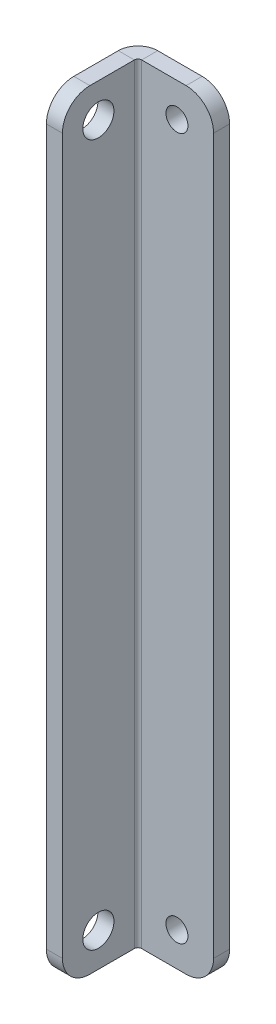
SolidWorks part; units mm, degrees
note: The reader was unsure of these and kept them because the rebuilt part matched: thickness of "Base-Flange1", "Edge-Flange1", "Sheet-Metal1", "Sheet-Metal2", "Sheet-Metal3", "Sheet-Metal4"; flange length of "Edge-Flange1".
ref_plane "Front Plane" through (0, 0, 0) normal (0, 0, 1) x (1, 0, 0)
ref_plane "Top Plane" through (0, 0, 0) normal (0, 1, 0) x (1, 0, 0)
ref_plane "Right Plane" through (0, 0, 0) normal (1, 0, 0) x (0, 0, -1)
sketch "Sketch1" plane through (0, 0, 0) normal (0, 0, 1) x (1, 0, 0)
  line L1 (0, 0) -> (10, 0)
  line L2 (0, 0) -> (0, 84)
  line L3 (0, 84) -> (10, 84)
  line L4 (10, 0) -> (10, 84)
  dimension "D1" = 10
  dimension "D2" = 84
base flange "Base-Flange1" sketch "Sketch1" thickness 1.75 reverse thickness direction no parameters "D1"=0.4
edge flange "Edge-Flange1" sketch "Sketch8" flange angle 90 flange length 10 flange position material inside bend radius 0.4 thickness 1.75 relief rectangular parameters "D1"=1.75, "D6"=10, "D8"=1
sketch "Sketch8" plane through (0, 0, 0) normal (-1, 0, 0) x (0, -1, 0)
  line L2 (-84, 0) -> (-84, 8.25)
  line L3 (-84, 8.25) -> (0, 8.25)
  line L4 (0, 8.25) -> (0, 0)
  line L7 (-84, 0) -> (0, 0) construction
  line L8 (-84, 0) -> (0, 0)
bend "EdgeBend1" bend radius 0.4 bend angle 90 parameters "D5"=1
sketch "Sketch9" plane through (0, 0, -1.75) normal (0, 0, -1) x (-1, 0, 0)
  line L0 (-6, 84) -> (-6, 80.3) construction
  line L1 (-2.15, 0) -> (-10, 0) construction
  line L2 (-6, 0) -> (-6, 3.7) construction
  line L3 (-10, 84) -> (-2.15, 84) construction
  line L5 (-10, 0) -> (-10, 84) construction
  dimension "D1" = 76.6
  dimension "D2" = 4
sketch "Sketch12" plane through (0, 0, 0) normal (-1, 0, 0) x (0, 0, 1)
  line L0 (4.325, 84) -> (4.325, 80.3) construction
  line L2 (4.325, 0) -> (4.325, 3.7) construction
  line L4 (8.25, 84) -> (0.4, 84) construction
  line L5 (0.4, 0) -> (8.25, 0) construction
  point P6 (4.325, 84)
  dimension "D1" = 76.6
hole_wizard "ssd-mounting-holes" positions "3DSketch2" profile "Sketch13" hole size "M2" standard "ANSI Metric" end condition up to next
sketch3d "3DSketch2"
  point P0 (6, 80.3, -1.75)
  point P3 (6, 3.7, -1.75)
sketch "Sketch13" plane through (6, 80.3, -1.75) normal (1, 0, 0) x (0, 1, 0)
  line L0 (0, 0) -> (0, 1.75)
  line L1 (0, 1.75) -> (1.2, 1.75)
  line L2 (1.2, 1.75) -> (1.2, 0)
  line L5 (1.2, 0) -> (0, 0)
  line L11 (0, -6.35) -> (0, 107.95) construction
  dimension "Thru Hole Dia." = 2.4
  dimension "Thru Hole Depth" = 1.75
hole_wizard "spine-mounting-holes" positions "Sketch14" profile "Sketch15" hole size "M3" standard "ANSI Metric" end condition up to next
sketch "Sketch14" plane through (1.75, 0, 0) normal (1, 0, 0) x (0, 0, -1)
  point P0 (-4.325, 80.3)
  point P3 (-4.325, 3.7)
sketch "Sketch15" plane through (1.75, 80.3, 4.325) normal (0, 1, 0) x (0, 0, -1)
  line L0 (0, 0) -> (0, 1.75)
  line L1 (0, 1.75) -> (1.7, 1.75)
  line L2 (1.7, 1.75) -> (1.7, 0)
  line L5 (1.7, 0) -> (0, 0)
  line L11 (0, -6.35) -> (0, 107.95) construction
  dimension "Thru Hole Dia." = 3.4
  dimension "Thru Hole Depth" = 1.75
fillet "Fillet1" radius 3 4 edges at (0.875, 0, 8.25) (10, 0, -0.875) (0.875, 84, 8.25) (10, 84, -0.875)
sketch "Bend-Lines1" [suppressed] plane through (0, 0, 0) normal (0, 1, 0) x (1, 0, 0)
sketch "Bounding-Box1" [suppressed] plane through (0, 0, 0) normal (0, 1, 0) x (1, 0, 0)
sheet metal parameters "Sheet-Metal1" thickness 1.75 parameters "D1"=1.016, "D7"=1.016
flat pattern "Flat-Pattern1" [suppressed]
sketch "Bend-Lines2" plane through (0, 0, 0) normal (0, 1, 0) x (1, 0, 0)
sketch3d "Bounding-Box2" [suppressed]
  line L0 (8.75, 82, 0) -> (8.75, 0, 0) construction
  line L1 (0, 82, 0) -> (0, 0, 0) construction
  line L2 (8.75, 82, 0) -> (0, 82, 0) construction
  line L3 (8.75, 0, 0) -> (0, 0, 0) construction
sheet metal parameters "Sheet-Metal2" thickness 1.75 parameters "D1"=1.016, "D7"=1.016
flat pattern "Flat-Pattern1" [suppressed]
sketch "Bend-Lines2" plane through (0, 0, 0) normal (0, 0, 1) x (1, 0, 0)
  line L0 (-0.1809, 82) -> (-0.1809, 0) construction
  line L1 (-0.1809, 82) -> (-0.1809, 0) construction
sketch3d "Bounding-Box2" [suppressed]
  line L0 (8.75, 82, 0) -> (8.75, 0, 0) construction
  line L1 (-9.1119, 82, 0) -> (-9.1119, 0, 0) construction
  line L2 (8.75, 82, 0) -> (-9.1119, 82, 0) construction
  line L3 (8.75, 0, 0) -> (-9.1119, 0, 0) construction
bend of the flat pattern "Flatten-<EdgeBend1>1"
sheet metal parameters "Sheet-Metal3" thickness 1.75 parameters "D1"=1.016, "D7"=1.016
flat pattern "Flat-Pattern1" [suppressed]
sketch "Bend-Lines2" plane through (0, 0, 0) normal (0, 0, 1) x (1, 0, 0)
  line L0 (-0.1809, 84) -> (-0.1809, 0) construction
  line L1 (-0.1809, 84) -> (-0.1809, 0) construction
sketch3d "Bounding-Box2" [suppressed]
  line L0 (8.75, 84, 0) -> (8.75, 0, 0) construction
  line L1 (-9.1119, 84, 0) -> (-9.1119, 0, 0) construction
  line L2 (8.75, 84, 0) -> (-9.1119, 84, 0) construction
  line L3 (8.75, 0, 0) -> (-9.1119, 0, 0) construction
sketch "Sketch12-1" plane through (-0.3619, 0, -1.016) normal (0, 0, -1) x (-1, 0, 0)
  line L0 (4.883, 84) -> (4.883, 80.3) construction
  line L2 (4.883, 0) -> (4.883, 3.7) construction
  dimension "D1" = 76.6
bend of the flat pattern "Flatten-<EdgeBend1>1"
sheet metal parameters "Sheet-Metal4" thickness 1.75 parameters "D1"=1.016, "D7"=1.016
flat pattern "Flat-Pattern1" [suppressed]
sketch "Bend-Lines2" plane through (0, 0, 0) normal (0, 0, 1) x (1, 0, 0)
  line L0 (1.1486, 84) -> (1.1486, 0) construction
  line L1 (1.1486, 84) -> (1.1486, 0) construction
sketch3d "Bounding-Box2" [suppressed]
  line L0 (10, 0, 0) -> (10, 84, 0) construction
  line L1 (-7.7028, 0, 0) -> (-7.7028, 84, 0) construction
  line L2 (10, 0, 0) -> (-7.7028, 0, 0) construction
  line L3 (10, 84, 0) -> (-7.7028, 84, 0) construction
bend of the flat pattern "Flatten-<EdgeBend1>1"
sketch "Sketch12-1" plane through (0.5472, 0, -1.75) normal (0, 0, -1) x (-1, 0, 0)
  line L0 (4.325, 84) -> (4.325, 80.3) construction
  line L2 (4.325, 0) -> (4.325, 3.7) construction
  dimension "D1" = 76.6
